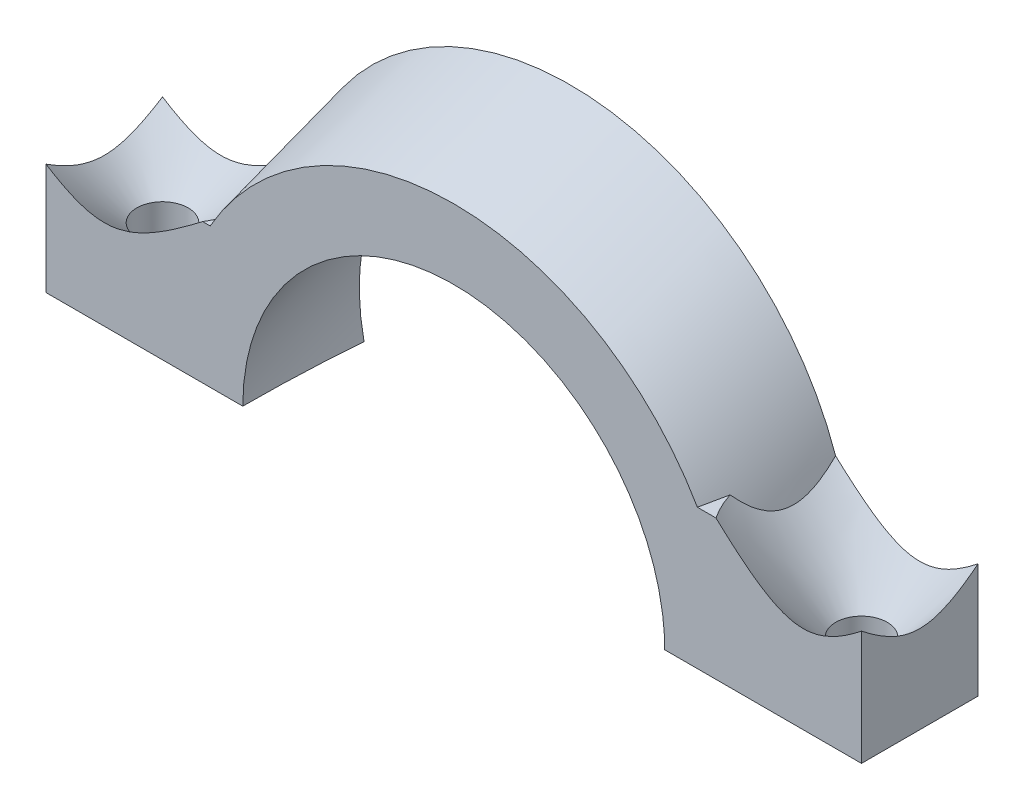
SolidWorks part; units mm, degrees
ref_plane "Front Plane" through (0, 0, 0) normal (0, 0, 1) x (1, 0, 0)
ref_plane "Top Plane" through (0, 0, 0) normal (0, 1, 0) x (1, 0, 0)
ref_plane "Right Plane" through (0, 0, 0) normal (1, 0, 0) x (0, 0, -1)
sketch "Sketch1" plane through (0, 0, 0) normal (0, 1, 0) x (1, 0, 0)
  line L1 (22.225, -47.625) -> (-22.225, -47.625)
  line L2 (22.225, -47.625) -> (22.225, 47.625)
  line L3 (22.225, 47.625) -> (-22.225, 47.625)
  line L4 (-22.225, -47.625) -> (-22.225, 47.625)
  line L5 (22.225, -47.625) -> (-22.225, 47.625) construction
  line L6 (22.225, 47.625) -> (-22.225, -47.625) construction
  point P0 (0, 0)
  dimension "D1" = 95.25
  dimension "D2" = 44.45
extrude "Boss-Extrude1" add sketch "Sketch1" along normal blind 3.175
sketch "Sketch2" plane through (0, 0, 0) normal (1, 0, 0) x (0, 0, -1)
  line L3 (-47.625, 3.175) -> (-47.625, 0) construction
  line L4 (-36.83, 3.175) -> (-36.83, 19.05)
  line L5 (-24.1873, 28.0503) -> (47.625, 3.175)
  line L6 (-47.625, 3.175) -> (47.625, 3.175)
  line L7 (-47.625, 3.175) -> (-35.5269, 23.859)
  line L8 (-17.78, 3.175) -> (-17.78, 19.05)
  circle A0 centre (-27.305, 19.05) radius 4
  arc A2 (-35.5269, 23.859) -> (-24.1873, 28.0503) centre (-27.305, 19.05) cw
  arc A3 (-17.78, 19.05) -> (-36.83, 19.05) centre (-27.305, 19.05) ccw
  point P6 (-47.625, 1.5875)
  dimension "D1" = 8
  dimension "D6" = 19.05
  dimension "D2" = 20.32
  dimension "D3" = 19.05
extrude "Boss-Extrude2" add sketch "Sketch2" along normal mid plane 44.45 contours A2 L6 L5 | A2 A0 | A3 L7 L6 L4 region at (0, 9.3974, 40.4061) region at (0, 14.4275, 27.305) region at (0, 10.8864, -3.7601)
extrude "Cut-Extrude1" cut sketch "Sketch2<3>" against normal mid plane 31.75 contours A3 L7 L6 L4 | A3 L8 L6 L5 region at (0, 9.3974, 40.4061) region at (0, 10.8864, -3.7601)
sketch "Sketch2<3>" plane through (0, 0, 0) normal (1, 0, 0) x (0, 0, -1) same geometry as "Sketch2"
extrude "Cut-Extrude2" cut sketch "Sketch2<4>" against normal mid plane 16.51 contours A2 A0 | A0 region at (0, 14.4275, 27.305) region at (0, 19.05, 27.305)
sketch "Sketch2<4>" plane through (0, 0, 0) normal (1, 0, 0) x (0, 0, -1) same geometry as "Sketch2"
sketch "Sketch3" plane through (0, 3.175, 0) normal (0, 1, 0) x (1, 0, 0)
  line L0 (-15.875, 0) -> (15.875, 0) construction
  line L5 (-15.875, -24.1873) -> (-15.875, 47.625) construction
  line L6 (15.875, -17.78) -> (15.875, 47.625) construction
  line L8 (-6.35, 43.005) -> (6.35, 43.005)
  line L9 (-6.35, 43.005) -> (-6.35, 37.005)
  line L10 (-6.35, 37.005) -> (6.35, 37.005)
  line L11 (6.35, 43.005) -> (6.35, 37.005)
  line L12 (-6.35, 43.005) -> (6.35, 37.005) construction
  line L13 (6.35, 43.005) -> (-6.35, 37.005) construction
  line L14 (-15.875, 47.625) -> (15.875, 47.625) construction
  line L15 (-6.35, -37.005) -> (6.35, -37.005)
  line L16 (6.35, -43.005) -> (6.35, -37.005)
  line L17 (-6.35, -43.005) -> (6.35, -43.005)
  line L18 (-6.35, -43.005) -> (-6.35, -37.005)
  point P11 (0, 37.005)
  point P12 (0, 40.005)
  dimension "D1" = 12.7
  dimension "D2" = 6
  dimension "D3" = 7.62
extrude "Cut-Extrude3" cut sketch "Sketch3" against normal through all
sketch "Sketch4" plane through (0, 3.175, 0) normal (0, 1, 0) x (1, 0, 0)
  line L0 (-22.225, -24.1873) -> (-22.225, 47.625) construction
  line L1 (-22.225, 32.385) -> (22.225, 32.385)
  line L2 (-22.225, 32.385) -> (-22.225, 26.035)
  line L3 (-22.225, 26.035) -> (22.225, 26.035)
  line L4 (22.225, 32.385) -> (22.225, 26.035)
  line L5 (22.225, -24.1873) -> (22.225, 47.625) construction
  line L6 (-6.35, 43.005) -> (-6.35, 37.005) construction
  point P10 (-6.35, 40.005)
  dimension "D1" = 7.62
  dimension "D2" = 6.35
extrude "Boss-Extrude3" add sketch "Sketch4" along normal blind 55.88
ref_plane "Plane1" through (0, 0, 0) normal (1, 0, 0) x (0, 0, -1)
sketch "Sketch5" plane through (0, 0, 0) normal (1, 0, 0) x (0, 0, -1)
  line L0 (-27.305, 19.05) -> (48.895, 19.05) construction
  line L1 (-27.305, 19.05) -> (43.8338, 46.3576)
  dimension "D1" = 76.2
  dimension "D2" = 76.2
  dimension "D3" = 21
sketch "Sketch6" plane through (0, 0, -26.035) normal (0, 0, 1) x (1, 0, 0)
  circle A0 centre (0, 39.5253) radius 11.5
  point P0 (0, 39.5253)
  dimension "D1" = 23
sweep "Cut-Sweep1" cut profiles "Sketch6" path "Sketch5"
sketch "Sketch10" plane through (0, 0, -26.035) normal (0, 0, 1) x (1, 0, 0)
  line L1 (-22.225, 59.055) -> (-22.225, 10.6536) construction
  line L2 (22.225, 59.055) -> (22.225, 10.6536) construction
  line L4 (-22.225, 39.5253) -> (-15.31, 39.5253)
  line L5 (15.31, 39.5253) -> (22.225, 39.5253)
  line L6 (-22.225, 39.5253) -> (-22.225, 59.055)
  line L7 (-22.225, 59.055) -> (22.225, 59.055)
  line L8 (22.225, 59.055) -> (22.225, 39.5253)
  circle A3 centre (0, 39.5253) radius 11.5 construction
  arc A4 (15.31, 39.5253) -> (-15.31, 39.5253) centre (0, 39.5253) ccw
  dimension "D2" = 3.81
sweep "Cut-Sweep4" cut profiles "Sketch10" path "Sketch5<4>"
sketch "Sketch5<4>" plane through (0, 0, 0) normal (1, 0, 0) x (0, 0, -1) same geometry as "Sketch5"
sketch "Sketch11" plane through (0, 0, -26.035) normal (0, 0, 1) x (1, 0, 0)
  line L0 (22.225, 39.5253) -> (22.225, 10.6536) construction
  line L1 (-22.225, 39.5253) -> (22.225, 39.5253)
  line L2 (-22.225, 39.5253) -> (-22.225, 47.1453)
  line L3 (-22.225, 47.1453) -> (22.225, 47.1453)
  line L4 (22.225, 39.5253) -> (22.225, 47.1453)
  arc A0 (15.31, 39.5253) -> (13.279, 47.1453) centre (0, 39.5253) ccw
  arc A1 (-13.279, 47.1453) -> (-15.31, 39.5253) centre (0, 39.5253) ccw
  line M6 (-15.31, 39.5253) -> (-22.225, 39.5253)
  line M14 (22.225, 39.5253) -> (15.31, 39.5253)
  arc M15 (15.31, 39.5253) -> (-15.31, 39.5253) centre (0, 39.5253) ccw
  dimension "D1" = 7.62
extrude "Boss-Extrude4" add sketch "Sketch11" against normal blind 6.35 contours L3 L2 M6 M15 | L4 L3 M14 M15 region at (-18.4148, 43.5031, -26.035) region at (18.4148, 43.5031, -26.035)
sketch "Sketch12" plane through (0, 47.1453, 0) normal (0, 1, 0) x (1, 0, 0)
  line L0 (-22.225, 32.385) -> (-22.225, 26.035) construction
  line L1 (-22.225, 32.385) -> (-15.875, 32.385) construction
  line L2 (0, 0) -> (0, 50.8)
  circle A0 centre (-19.05, 29.21) radius 1.4
  circle A1 centre (19.05, 29.21) radius 1.4
  dimension "D3" = 2.8
  dimension "D1" = 3.175
  dimension "D2" = 3.175
  dimension "D4" = 50.8
extrude "Cut-Extrude4" cut sketch "Sketch12" against normal blind 18.75 contours A0 | A1 region at (-19.05, 47.1453, -29.21) region at (19.05, 47.1453, -29.21)
chamfer "Chamfer1" distance 4.83 distance2 4.32 2 edges at (19.05, 47.1453, -27.81) (-19.05, 47.1453, -27.81) first distance on face at (19.05, 28.3953, -27.81) first distance on face at (-19.05, 47.1453, -27.81)
sketch "Sketch13" plane through (0, 0, -26.035) normal (0, 0, 1) x (1, 0, 0)
  line L1 (-35.3917, 39.5253) -> (31.1619, 39.5253)
  line L2 (-35.3917, 39.5253) -> (-35.3917, -4.1635)
  line L3 (-35.3917, -4.1635) -> (31.1619, -4.1635)
  line L4 (31.1619, 39.5253) -> (31.1619, -4.1635)
extrude "Cut-Extrude5" cut sketch "Sketch13" against normal through all both and the other way through all
